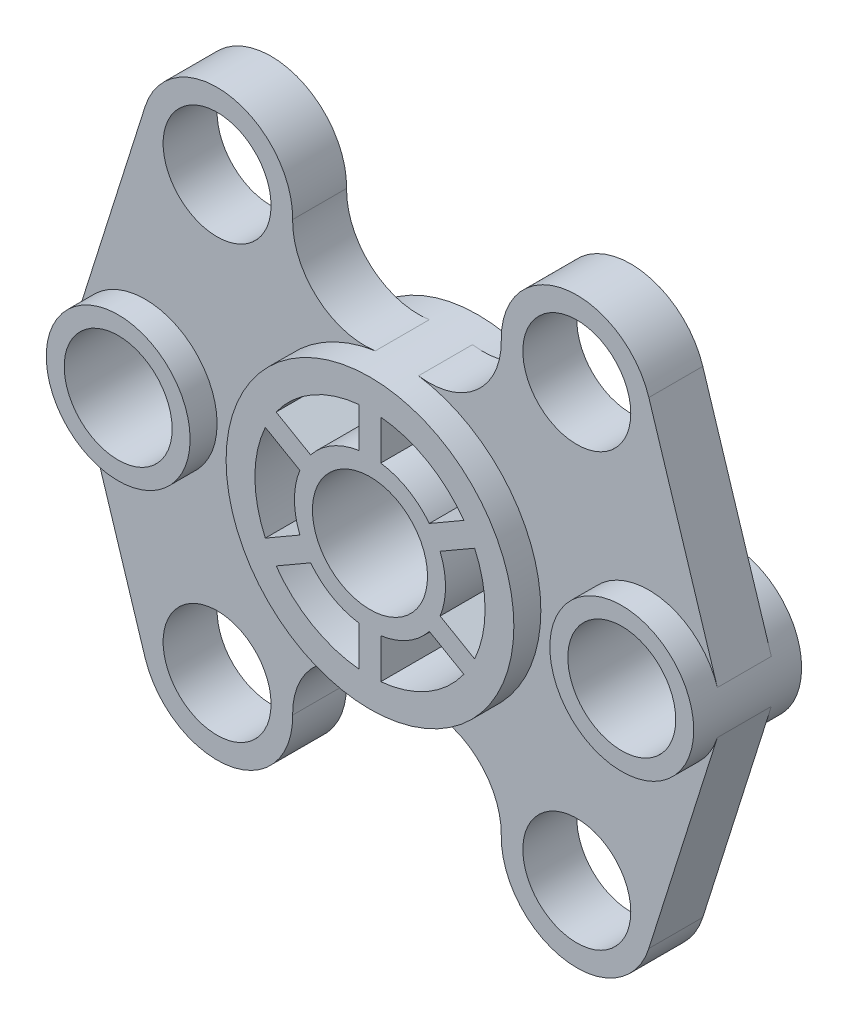
SolidWorks part; units mm, degrees
ref_plane "Front Plane" through (0, 0, 0) normal (0, 0, 1) x (1, 0, 0)
ref_plane "Top Plane" through (0, 0, 0) normal (0, 1, 0) x (1, 0, 0)
ref_plane "Right Plane" through (0, 0, 0) normal (1, 0, 0) x (0, 0, -1)
sketch "Sketch1" plane through (0, 0, 0) normal (0, 0, 1) x (1, 0, 0)
  line L0 (0, 0) -> (0, 79710.6442) construction
  line L1 (0, 0) -> (79710.6442, 0) construction
  line L14 (-3, -20.7846) -> (-3, -31.8591)
  line L15 (3, -20.7846) -> (3, -31.8591)
  line L16 (-19.5, -7.7942) -> (-29.0908, -13.3315)
  line L17 (-16.5, -12.9904) -> (-26.0908, -18.5276)
  line L18 (-16.5, 12.9904) -> (-26.0908, 18.5276)
  line L19 (-19.5, 7.7942) -> (-29.0908, 13.3315)
  line L20 (3, 20.7846) -> (3, 31.8591)
  line L21 (-3, 20.7846) -> (-3, 31.8591)
  line L22 (19.5, 7.7942) -> (29.0908, 13.3315)
  line L23 (16.5, 12.9904) -> (26.0908, 18.5276)
  line L24 (16.5, -12.9904) -> (26.0908, -18.5276)
  line L25 (19.5, -7.7942) -> (29.0908, -13.3315)
  line L26 (-89.0713, -6.0238) -> (-70.0249, -66.325)
  line L27 (-89.0713, 6.0238) -> (-70.0249, 66.325)
  line L28 (89.0713, -6.0238) -> (70.0249, -66.325)
  line L29 (89.0713, 6.0238) -> (70.0249, 66.325)
  circle A14 centre (0, 0) radius 16
  arc A15 (-19.5, 7.7942) -> (-19.5, -7.7942) centre (0, 0) ccw
  arc A16 (-29.0908, 13.3315) -> (-29.0908, -13.3315) centre (0, 0) ccw
  circle A17 centre (0, 0) radius 40
  circle A18 centre (-70, 0) radius 15
  circle A19 centre (-70, 0) radius 20
  circle A20 centre (-50, -60) radius 15
  circle A21 centre (-50, 60) radius 15
  arc A22 (-70.0249, -66.325) -> (-29.0029, -59.6519) centre (-50, -60) ccw
  arc A23 (-29.0029, -59.6519) -> (-6.0038, -39.5469) centre (-9.0056, -59.3203) cw
  arc A24 (70.0249, -66.325) -> (29.0029, -59.6519) centre (50, -60) cw
  arc A25 (29.0029, -59.6519) -> (6.0038, -39.5469) centre (9.0056, -59.3203) ccw
  arc A26 (-29.0029, 59.6519) -> (-6.0038, 39.5469) centre (-9.0056, 59.3203) ccw
  arc A27 (-70.0249, 66.325) -> (-29.0029, 59.6519) centre (-50, 60) cw
  circle A28 centre (50, -60) radius 15
  circle A29 centre (70, 0) radius 15
  circle A30 centre (70, 0) radius 20
  circle A31 centre (50, 60) radius 15
  arc A32 (70.0249, 66.325) -> (29.0029, 59.6519) centre (50, 60) ccw
  arc A33 (29.0029, 59.6519) -> (6.0038, 39.5469) centre (9.0056, 59.3203) cw
  arc A34 (-16.5, -12.9904) -> (-3, -20.7846) centre (0, 0) ccw
  arc A35 (-26.0908, -18.5276) -> (-3, -31.8591) centre (0, 0) ccw
  arc A36 (3, -20.7846) -> (16.5, -12.9904) centre (0, 0) ccw
  arc A37 (3, -31.8591) -> (26.0908, -18.5276) centre (0, 0) ccw
  arc A38 (19.5, -7.7942) -> (19.5, 7.7942) centre (0, 0) ccw
  arc A39 (29.0908, -13.3315) -> (29.0908, 13.3315) centre (0, 0) ccw
  arc A40 (26.0908, 18.5276) -> (3, 31.8591) centre (0, 0) ccw
  arc A41 (16.5, 12.9904) -> (3, 20.7846) centre (0, 0) ccw
  arc A42 (-3, 31.8591) -> (-26.0908, 18.5276) centre (0, 0) ccw
  arc A43 (-3, 20.7846) -> (-16.5, 12.9904) centre (0, 0) ccw
  point P37 (0, 0)
  dimension "D1" = 32
  dimension "D2" = 42
  dimension "D3" = 64
  dimension "D4" = 80
  dimension "D7" = 30
  dimension "D8" = 40
  dimension "D11" = 30
  dimension "D13" = 21
  dimension "D14" = 20
  dimension "D6" = 6
  dimension "D5" = 6
  dimension "D9" = 60
  dimension "D10" = 50
  dimension "D12" = 20
extrude "Boss-Extrude1" add sketch "Sketch1" along normal mid plane 30 contours A19 A18 | A17 A39 L25 A38 L22 A37 L15 A36 L24 A35 L17 A34 L14 A14 A16 L19 A15 L16 L23 A41 L20 A40 L21 A43 L18 A42 | A30 A29 region at (-89.4343, 0, 0) region at (-38.8686, 0, 0) region at (50.5657, 0, 0)
extrude "Boss-Extrude2" add sketch "Sketch1<3>" along normal mid plane 15 contours A27 L27 A19 L26 A22 A23 A17 A26 A20 A21 | A32 A33 A17 A25 A24 L28 A30 L29 A28 A31 region at (-66.6751, -21.5658, 0) region at (31.7133, -27.2622, 0)
sketch "Sketch1<3>" plane through (0, 0, 0) normal (0, 0, 1) x (1, 0, 0) same geometry as "Sketch1"
